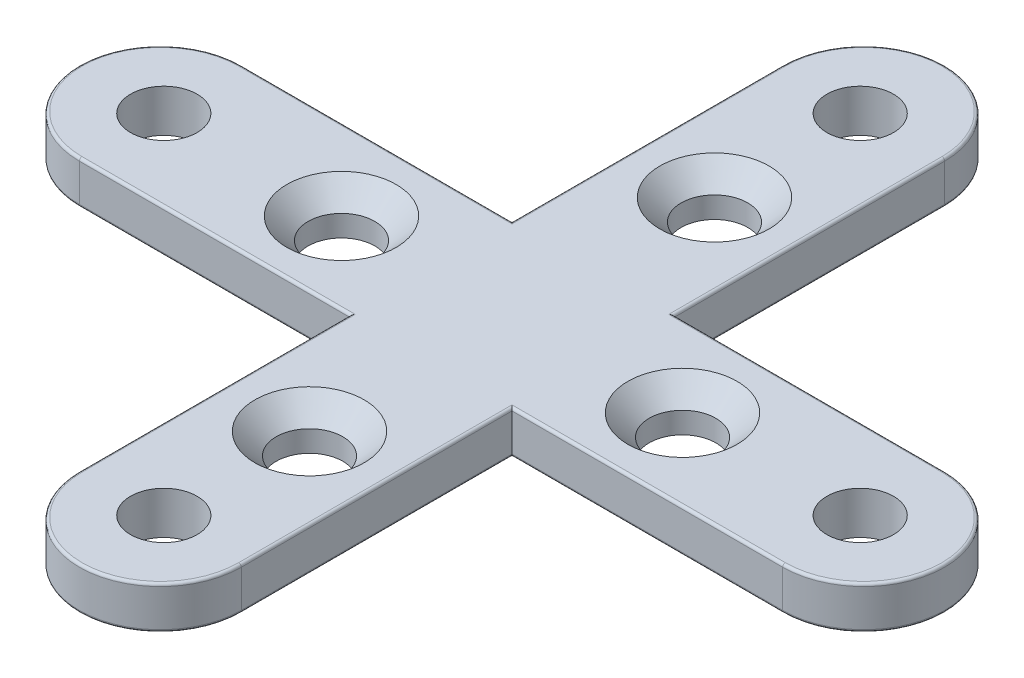
SolidWorks part; units mm, degrees
ref_plane "Front Plane" through (0, 0, 0) normal (0, 0, 1) x (1, 0, 0)
ref_plane "Top Plane" through (0, 0, 0) normal (0, 1, 0) x (1, 0, 0)
ref_plane "Right Plane" through (0, 0, 0) normal (1, 0, 0) x (0, 0, -1)
sketch "Sketch1" plane through (0, 0, 0) normal (0, 1, 0) x (1, 0, 0)
  line L0 (0, -16.5) -> (0, 16.5) construction
  line L1 (-3.8, -16.5) -> (-3.8, 16.5)
  line L2 (3.8, -16.5) -> (3.8, 16.5)
  line L3 (0, 0) -> (10.8491, 0) construction
  arc A0 (-3.8, -16.5) -> (3.8, -16.5) centre (0, -16.5) ccw
  arc A1 (3.8, 16.5) -> (-3.8, 16.5) centre (0, 16.5) ccw
  circle A2 centre (0, 16.3375) radius 1.5625
  circle A3 centre (0, -16.3375) radius 1.5625
  point P2 (0, 0)
  point P8 (0, 20.3)
  point P9 (0, -20.3)
  point P12 (0, 17.9)
  dimension "D4" = 3.125
  dimension "D1" = 7.6
  dimension "D2" = 40.6
  dimension "D3" = 2.4
extrude "Boss-Extrude1" add sketch "Sketch1" along normal blind 2
sketch3d "3DSketch1"
  line L0 (0, 0, 0) -> (0, 3, 0) construction
  dimension "D1" = 3
pattern_circular "CirPattern1" count 2 over 90 about axis through (0, 0, 0) along (0, 1, 0) of "Boss-Extrude1"
sketch "Sketch2" plane through (0, 0, 0) normal (0, 1, 0) x (1, 0, 0)
  line L0 (0, 0) -> (-1.9282, 0) construction
  line L1 (0, 0) -> (0, -2.0384) construction
  circle A0 centre (0, 9.5) radius 1.5625
  circle A1 centre (8, 0) radius 1.5625
  circle A2 centre (0, -9.5) radius 1.5625
  circle A3 centre (-8, 0) radius 1.5625
  dimension "D1" = 3.125
  dimension "D2" = 8
  dimension "D3" = 9.5
extrude "Cut-Extrude1" cut sketch "Sketch2" along normal up to surface (2 mm away) up to face at (0, 2, 0)
chamfer "Chamfer1" distance 1 angle 45 4 edges at (-8, 2, 1.5625) (0, 2, 11.0625) (8, 2, 1.5625) (0, 2, -7.9375)
fillet "Fillet1" radius 0.125 24 edges at (10.15, 2, 3.8) (20.3, 2, 0) (3.8, 2, 10.15) (0, 2, 20.3) (-10.15, 2, 3.8) (-20.3, 2, 0) (3.8, 2, -10.15) (0, 2, -20.3) (3.8, 0, -10.15) (0, 0, -20.3) (10.15, 0, -3.8) (20.3, 0, 0) (3.8, 0, 10.15) (0, 0, 20.3) (-10.15, 0, -3.8) (-10.15, 0, 3.8) (10.15, 2, -3.8) (-3.8, 2, 10.15) (-10.15, 2, -3.8) (-3.8, 2, -10.15) (-3.8, 0, -10.15) (10.15, 0, 3.8) (-3.8, 0, 10.15) (-20.3, 0, 0)
